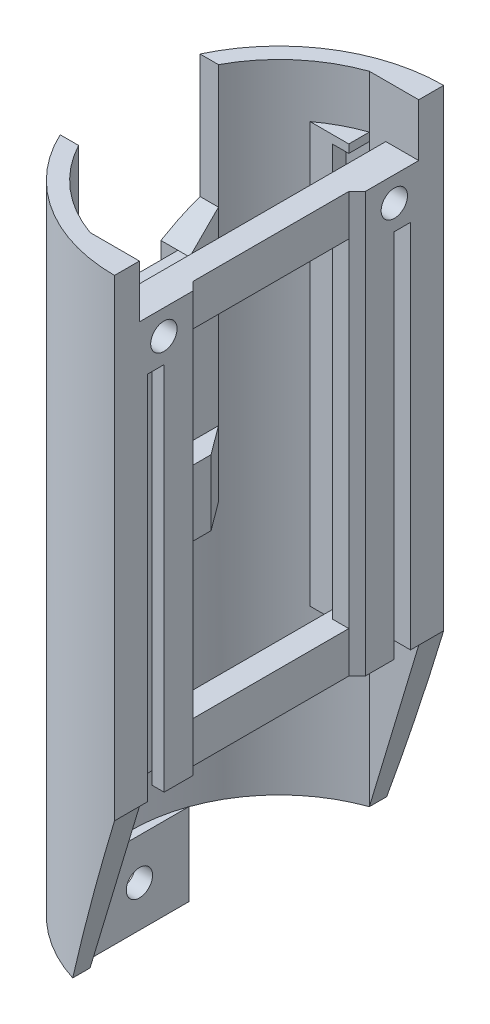
SolidWorks part; units mm, degrees
ref_plane "前视基准面" through (0, 0, 0) normal (0, 0, 1) x (1, 0, 0)
ref_plane "上视基准面" through (0, 0, 0) normal (0, 1, 0) x (1, 0, 0)
ref_plane "右视基准面" through (0, 0, 0) normal (1, 0, 0) x (0, 0, -1)
other "Configuration Table"
sketch "草图1" plane through (0, 0, 0) normal (0, 1, 0) x (1, 0, 0)
  line L0 (0, -473.638) -> (0, 23208.2609) construction
  line L1 (0, 0) -> (-4, 0) construction
  line L2 (0, 20) -> (0, -20)
  line L3 (-4, -17.5499) -> (-4, 17.5499)
  arc A0 (0, 20) -> (0, -20) centre (0, 0) ccw
  arc A1 (-4, 17.5499) -> (-4, -17.5499) centre (0, 0) ccw
  point P12 (-4, 0)
  dimension "D1" = 40
  dimension "D2" = 36
  dimension "D3" = 4
extrude "凸台-拉伸1" add sketch "草图1" along normal blind 70
sketch "草图3" plane through (0, 0, 0) normal (1, 0, 0) x (0, 0, -1)
  line L0 (-20, 0) -> (20, 0) construction
  line L1 (-16, 60) -> (16, 60) construction
  line L2 (-16, 60) -> (-16, 0) construction
  line L3 (-16, 0) -> (16, 0) construction
  line L4 (16, 60) -> (16, 0) construction
  line L5 (-20, 70) -> (20, 70) construction
  circle A0 centre (-14, 58) radius 2 construction
  circle A1 centre (14, 58) radius 2 construction
  circle A2 centre (-14, 58) radius 1
  circle A3 centre (14, 58) radius 1
  point P4 (0, 60)
  dimension "D4" = 4
  dimension "D5" = 4
  dimension "D6" = 2
  dimension "D7" = 2
  dimension "D1" = 0
  dimension "D2" = 10
  dimension "D3" = 32
extrude "切除-拉伸2" cut sketch "草图3" against normal up to surface (4 mm away) from surface up to face at (-4, 35, 0) starting at face at (0, 35, 0)
sketch "草图5" plane through (0, 0, 0) normal (0, 1, 0) x (1, 0, 0)
  line L0 (0, -1000) -> (0, 49000) construction
  line L1 (-1000, 0) -> (49000, 0) construction
  line L2 (-6, 16.9706) -> (6, 16.9706) construction
  line L3 (-6, -16.9706) -> (6, -16.9706) construction
  line L4 (0, 16.9706) -> (0, -16.9706)
  line L5 (0, -16.9706) -> (-4, -16.9706)
  line L6 (-4, -17.5499) -> (-4, 17.5499) construction
  line L7 (-4, -16.9706) -> (-4, 16.9706)
  line L8 (-4, 16.9706) -> (0, 16.9706)
  circle A0 centre (0, 0) radius 18 construction
  point P11 (0, 16.9706)
  dimension "D1" = 12
extrude "切除-拉伸4" cut sketch "草图5" against normal blind 9 from surface starting at face at (-10, 70, 0)
sketch "草图6" plane through (0, 0, 0) normal (0, 1, 0) x (1, 0, 0)
  line L0 (-4, 16.9706) -> (-6, 16.9706)
  line L1 (0, 16.9706) -> (0, 18)
  line L2 (-4, -16.9706) -> (-6, -16.9706)
  line L3 (0, -16.9706) -> (0, -18)
  line L4 (-4, 16.9706) -> (-4, -16.9706)
  line L5 (0, 16.9706) -> (-4, 16.9706)
  line L6 (0, -16.9706) -> (0, 16.9706)
  line L7 (-4, -16.9706) -> (0, -16.9706)
  line L9 (0, 16.9706) -> (-4, 16.9706)
  line L11 (-4, -16.9706) -> (0, -16.9706)
  arc A0 (0, 18) -> (-6, 16.9706) centre (0, 0) ccw
  arc A1 (-6, -16.9706) -> (0, -18) centre (0, 0) ccw
  dimension "D1" = 0
extrude "凸台-拉伸2" add sketch "草图6" against normal up to surface from surface up to face at (-10, 0, 0) starting at face at (-6.25, 70, 0)
sketch "草图7" plane through (0, 0, 0) normal (0, 1, 0) x (1, 0, 0)
  line L4 (-4, 16.9706) -> (-4, -16.9706)
  line L5 (0, 16.9706) -> (-4, 16.9706)
  line L6 (0, -16.9706) -> (0, 16.9706)
  line L7 (-4, -16.9706) -> (0, -16.9706)
  line L8 (-4, 16.9706) -> (-4, -16.9706)
  line L9 (0, 16.9706) -> (-4, 16.9706)
  line L10 (0, -16.9706) -> (0, 16.9706)
  line L11 (-4, -16.9706) -> (0, -16.9706)
  dimension "D1" = 0
extrude "切除-拉伸5" cut sketch "草图7" along normal blind 10
sketch "草图8" plane through (0, 0, 0) normal (0, 1, 0) x (1, 0, 0)
  line L0 (0, 16.9706) -> (0, -16.9706) construction
  line L1 (-6, 16.9706) -> (0, 16.9706)
  line L2 (-6, 16.9706) -> (-6, 14.4706)
  line L3 (-6, 14.4706) -> (0, 14.4706)
  line L4 (0, 16.9706) -> (0, 14.4706)
  line L6 (0, -16.9706) -> (-6, -16.9706)
  line L7 (0, -16.9706) -> (0, -14.4706)
  line L8 (0, -14.4706) -> (-6, -14.4706)
  line L9 (-6, -16.9706) -> (-6, -14.4706)
  dimension "D1" = 2.5
  dimension "D2" = 2.5
extrude "凸台-拉伸3" add sketch "草图8" against normal blind 1 from surface starting at face at (-2, 61, 0)
sketch "草图10" plane through (0, 0, 0) normal (0, 1, 0) x (1, 0, 0)
  line L0 (-6, 16.9706) -> (-6, 14.4706)
  line L1 (-6, 14.4706) -> (-10.7053, 14.4706)
  line L2 (-6, -14.4706) -> (-10.7053, -14.4706)
  line L3 (-6, -14.4706) -> (-6, -16.9706)
  arc A0 (-6, 16.9706) -> (-10.7053, 14.4706) centre (0, 0) ccw
  arc A1 (-10.7053, -14.4706) -> (-6, -16.9706) centre (0, 0) ccw
extrude "凸台-拉伸4" add sketch "草图10" along normal up to surface (70 mm away) from surface up to face at (-7.3333, 70, 0) starting at face at (-7.3333, 0, 0)
sketch "草图11" plane through (0, 0, 0) normal (0, 1, 0) x (1, 0, 0)
  line L0 (0, 16.9706) -> (0, -16.9706) construction
  line L1 (-6, 16.9706) -> (0, 16.9706)
  line L2 (-6, 16.9706) -> (-6, 14.4706)
  line L3 (-6, 14.4706) -> (0, 14.4706)
  line L4 (0, 16.9706) -> (0, 14.4706)
  line L5 (-6, 14.4706) -> (-10.7053, 14.4706) construction
  line L7 (-6, -14.4706) -> (0, -14.4706)
  line L8 (-6, -14.4706) -> (-6, -16.9706)
  line L9 (-6, -16.9706) -> (0, -16.9706)
  line L10 (0, -14.4706) -> (0, -16.9706)
  dimension "D1" = 0
extrude "凸台-拉伸5" add sketch "草图11" along normal up to surface (70 mm away) from surface up to face at (-7.2705, 70, 0) starting at face at (-4, 61, 0)
sketch "草图12" plane through (0, 0, 0) normal (0, 0, 1) x (1, 0, 0)
  line L1 (-6, 60) -> (-4, 60)
  line L2 (-6, 60) -> (-6, 61)
  line L3 (-6, 61) -> (-4, 61)
  line L4 (-4, 60) -> (-4, 61)
extrude "切除-拉伸6" cut sketch "草图12" against normal up to surface (16.9706 mm away) from surface up to face at (-3.3333, 23.3333, -16.9706) starting at face at (-3.3333, 23.3333, 16.9706)
sketch "草图14" plane through (0, 0, 0) normal (0, 1, 0) x (1, 0, 0)
  line L0 (-4, -14.4706) -> (-4, 14.4706) construction
  line L1 (-4, 10.4706) -> (-3, 10.4706)
  line L2 (-4, 10.4706) -> (-4, -10.4706)
  line L3 (-4, -10.4706) -> (-3, -10.4706)
  line L4 (-3, 10.4706) -> (-3, -10.4706)
  line L5 (-10.7053, -14.4706) -> (0, -14.4706) construction
  line L6 (-4, 14.4706) -> (0, 14.4706) construction
  line L7 (0, 14.4706) -> (0, -14.4706) construction
  line L8 (-1, 10.4706) -> (0, 10.4706)
  line L9 (-1, 10.4706) -> (-1, -10.4706)
  line L10 (-1, -10.4706) -> (0, -10.4706)
  line L11 (0, 10.4706) -> (0, -10.4706)
  line L12 (0, -14.4706) -> (-4, -14.4706) construction
  line L13 (0, 14.4706) -> (-10.7053, 14.4706) construction
  dimension "D1" = 1
  dimension "D2" = 4
  dimension "D3" = 4
  dimension "D4" = 1
  dimension "D5" = 4
  dimension "D6" = 4
extrude "切除-拉伸8" cut sketch "草图14" along normal up to surface (61 mm away) from surface up to face at (-2, 61, 0) starting at face at (-2, 10, 0)
sketch "草图15" plane through (0, 0, 0) normal (1, 0, 0) x (0, 0, -1)
  line L0 (10.4706, 61) -> (10.4706, 10) construction
  line L5 (-10.4706, 61) -> (-10.4706, 10) construction
  line L6 (10.4706, 61) -> (-10.4706, 61) construction
  line L7 (-10.4706, 10) -> (10.4706, 10) construction
  line L9 (-9.4706, 56) -> (9.4706, 56)
  line L10 (-9.4706, 56) -> (-9.4706, 15)
  line L11 (-9.4706, 15) -> (9.4706, 15)
  line L12 (9.4706, 56) -> (9.4706, 15)
  dimension "D1" = 1
  dimension "D2" = 1
  dimension "D3" = 5
  dimension "D4" = 5
extrude "切除-拉伸9" cut sketch "草图15" against normal up to surface (3 mm away) from surface up to face at (-3, 35.5, 0) starting at face at (-1, 35.5, 0)
sketch "草图17" plane through (0, 0, 0) normal (1, 0, 0) x (0, 0, -1)
  circle A0 centre (-14, 58) radius 1.6
  circle A1 centre (14, 58) radius 1.6
  dimension "D1" = 3.2
  dimension "D2" = 3.2
extrude "切除-拉伸10" cut sketch "草图17" against normal blind 2.5
sketch "草图20" plane through (0, 0, 0) normal (0, 1, 0) x (1, 0, 0)
  line L0 (-1, 10.4706) -> (0, 10.4706)
  line L1 (0, 14.4706) -> (0, 10.4706) construction
  line L2 (0, 10.4706) -> (-1, 10.4706) construction
  line L3 (0, 10.4706) -> (-1, 9.4706)
  line L4 (-1, 10.4706) -> (-1, -10.4706) construction
  line L5 (-1, 9.4706) -> (-1, 10.4706)
  line L6 (-4, 10.4706) -> (-3, 10.4706)
  line L7 (-3, 10.4706) -> (-3, 9.4706)
  line L8 (-3, -10.4706) -> (-3, 10.4706) construction
  line L9 (-3, 9.4706) -> (-4, 10.4706)
  line L10 (-4, -10.4706) -> (-3, -10.4706)
  line L11 (-3, -10.4706) -> (-3, -9.4706)
  line L12 (-3, -9.4706) -> (-4, -10.4706)
  line L13 (0, -10.4706) -> (-1, -10.4706)
  line L14 (-1, -10.4706) -> (0, -10.4706) construction
  line L15 (-1, -10.4706) -> (-1, -9.4706)
  line L16 (-1, -9.4706) -> (0, -10.4706)
  dimension "D1" = 1
  dimension "D2" = 1
  dimension "D3" = 1
  dimension "D4" = 1
  dimension "D5" = 1
extrude "凸台-拉伸11" add sketch "草图20" against normal up to surface (-10 mm away) from surface up to face at (-2, 10, 0) starting at face at (-2, 61, 0)
sketch "草图21" plane through (0, 0, 0) normal (0, 1, 0) x (1, 0, 0)
  line L0 (-4, 10.4706) -> (-4, -10.4706)
  line L1 (-4, -10.4706) -> (-3, -9.4706)
  line L2 (-3, -9.4706) -> (-3, 9.4706)
  line L3 (-3, 9.4706) -> (-4, 10.4706)
extrude "凸台-拉伸12" add sketch "草图21" against normal up to surface (-56 mm away) from surface up to face at (-2, 56, 0) starting at face at (-2, 61, 0)
sketch "草图22" plane through (0, 0, 0) normal (0, 1, 0) x (1, 0, 0)
  line L4 (-4, 10.4706) -> (-4, -10.4706)
  line L5 (-4, -10.4706) -> (-3, -9.4706)
  line L6 (-3, -9.4706) -> (-3, 9.4706)
  line L7 (-3, 9.4706) -> (-4, 10.4706)
  line L8 (-4, 10.4706) -> (-4, -10.4706)
  line L9 (-4, -10.4706) -> (-3, -9.4706)
  line L10 (-3, -9.4706) -> (-3, 9.4706)
  line L11 (-3, 9.4706) -> (-4, 10.4706)
  dimension "D1" = 0
extrude "凸台-拉伸13" add sketch "草图22" along normal up to surface (15 mm away) from surface up to face at (-2, 15, 0) starting at face at (-2, 10, 0)
sketch "草图23" plane through (0, 0, 0) normal (0, 0, 1) x (1, 0, 0)
  line L0 (-3, 56) -> (-1, 56) construction
  line L1 (-6, 61) -> (-8, 61)
  line L2 (-6, 61) -> (-6, 55)
  line L3 (-6, 55) -> (-8, 55)
  line L4 (-8, 61) -> (-8, 55)
  dimension "D1" = 1
  dimension "D2" = 2
extrude "切除-拉伸11" cut sketch "草图23" along normal up to surface (1.654 mm away) from surface up to face at (-14.3526, 35, 0) starting at face at (-5.3444, 46.1429, 14.4706)
sketch "草图24" plane through (0, 0, 0) normal (0, 0, 1) x (1, 0, 0)
  line L4 (-6, 61) -> (-8, 61)
  line L5 (-8, 61) -> (-8, 55)
  line L6 (-8, 55) -> (-6, 55)
  line L7 (-6, 55) -> (-6, 61)
  line L8 (-6, 61) -> (-8, 61)
  line L9 (-8, 61) -> (-8, 55)
  line L10 (-8, 55) -> (-6, 55)
  line L11 (-6, 55) -> (-6, 61)
  dimension "D1" = 0
extrude "切除-拉伸12" cut sketch "草图24" against normal up to surface (16.1245 mm away) up to face at (-14.3526, 35, 0)
sketch "草图25" plane through (0, 0, 0) normal (0, 1, 0) x (1, 0, 0)
  line L0 (-6, -16.9706) -> (-6, -14.4706)
  line L1 (-8, -14.4706) -> (-4, -14.4706) construction
  line L2 (-6, -14.4706) -> (-10.7053, -14.4706)
  line L3 (-10.7053, 14.4706) -> (-6, 14.4706)
  line L4 (-4, 14.4706) -> (-8, 14.4706) construction
  line L5 (-6, 14.4706) -> (-6, 16.9706)
  arc A0 (-10.7053, -14.4706) -> (-6, -16.9706) centre (0, 0) ccw
  arc A1 (-6, 16.9706) -> (-10.7053, 14.4706) centre (0, 0) ccw
extrude "切除-拉伸13" cut sketch "草图25" along normal up to surface (10 mm away) from surface up to face at (-1.25, 10, 0) starting at face at (-7.2705, 0, 0)
sketch "草图29" plane through (0, 0, 0) normal (0, 1, 0) x (1, 0, 0)
  line L0 (0, -16.9706) -> (0, -14.4706)
  line L1 (0, -14.4706) -> (-10.7053, -14.4706)
  line L2 (0, -16.9706) -> (-6, -16.9706)
  line L3 (-4, -16.9706) -> (-6, -16.9706)
  line L4 (0, -18) -> (0, -16.9706)
  line L5 (0, -16.9706) -> (-4, -16.9706)
  line L6 (-4, -16.9706) -> (-6, -16.9706) construction
  line L8 (0, -16.9706) -> (-4, -16.9706) construction
  line L9 (-6, 16.9706) -> (-4, 16.9706)
  line L10 (0, 16.9706) -> (0, 18)
  line L11 (-4, 16.9706) -> (0, 16.9706)
  line L12 (-6, 16.9706) -> (-4, 16.9706) construction
  line L14 (-4, 16.9706) -> (0, 16.9706) construction
  line L15 (-6, 16.9706) -> (0, 16.9706)
  line L16 (0, 16.9706) -> (0, 14.4706)
  line L17 (0, 14.4706) -> (-10.7053, 14.4706)
  arc A0 (-10.7053, -14.4706) -> (-6, -16.9706) centre (0, 0) ccw
  arc A1 (-6, -16.9706) -> (0, -18) centre (0, 0) ccw
  arc A3 (0, 18) -> (-6, 16.9706) centre (0, 0) ccw
  arc A5 (-6, 16.9706) -> (-10.7053, 14.4706) centre (0, 0) ccw
  dimension "D1" = 0
  dimension "D2" = 0
extrude "切除-拉伸18" cut sketch "草图29" against normal up to surface (-61 mm away) from surface up to face at (-1.25, 61, 0) starting at face at (-8.1175, 70, 0)
sketch "草图30" plane through (0, 0, 0) normal (0, 1, 0) x (1, 0, 0)
  line L0 (-8, 16.1245) -> (-8, 14.4706)
  line L1 (-8, 14.4706) -> (-4, 14.4706)
  line L2 (-4, -16.9706) -> (-4, 16.9706) construction
  line L3 (-4, 14.4706) -> (-4, 16.9706)
  line L4 (-6, 16.9706) -> (0, 16.9706) construction
  line L5 (-4, 16.9706) -> (-6, 16.9706)
  line L6 (-8, -16.1245) -> (-8, -14.4706)
  line L7 (-8, -14.4706) -> (-4, -14.4706)
  line L8 (-4, -14.4706) -> (-4, -16.9706)
  line L9 (-4, -16.9706) -> (-6, -16.9706)
  arc A0 (-6, 16.9706) -> (-8, 16.1245) centre (0, 0) ccw
  arc A1 (-8, -16.1245) -> (-6, -16.9706) centre (0, 0) ccw
extrude "凸台-拉伸16" add sketch "草图30" against normal blind 1 from surface starting at face at (-8.9139, 61, -15.0418)
sketch "草图31" plane through (0, 0, 0) normal (0, 1, 0) x (1, 0, 0)
  line L4 (0, -20) -> (0, -16.9706)
  line L5 (0, -16.9706) -> (-6, -16.9706)
  line L6 (-6, 16.9706) -> (0, 16.9706)
  line L7 (0, 16.9706) -> (0, 20)
  line L8 (0, -20) -> (0, -16.9706)
  line L9 (0, -16.9706) -> (-6, -16.9706)
  line L10 (-6, 16.9706) -> (0, 16.9706)
  line L11 (0, 16.9706) -> (0, 20)
  arc A2 (-6, 16.9706) -> (-6, -16.9706) centre (0, 0) ccw
  arc A3 (0, 20) -> (0, -20) centre (0, 0) ccw
  arc A4 (-6, 16.9706) -> (-6, -16.9706) centre (0, 0) ccw
  arc A5 (0, 20) -> (0, -20) centre (0, 0) ccw
  dimension "D1" = 0
extrude "凸台-拉伸17" add sketch "草图31" along normal blind 2.4 from surface starting at face at (-7.3333, 70, 0)
sketch "草图32" plane through (0, 0, 0) normal (0, 1, 0) x (1, 0, 0)
  line L4 (0, 16.9706) -> (0, 20)
  line L5 (0, -20) -> (0, -16.9706)
  line L6 (0, -16.9706) -> (-6, -16.9706)
  line L7 (-6, 16.9706) -> (0, 16.9706)
  line L8 (0, 16.9706) -> (0, 20)
  line L9 (0, -20) -> (0, -16.9706)
  line L10 (0, -16.9706) -> (-6, -16.9706)
  line L11 (-6, 16.9706) -> (0, 16.9706)
  arc A2 (0, 20) -> (0, -20) centre (0, 0) ccw
  arc A3 (-6, 16.9706) -> (-6, -16.9706) centre (0, 0) ccw
  arc A4 (0, 20) -> (0, -20) centre (0, 0) ccw
  arc A5 (-6, 16.9706) -> (-6, -16.9706) centre (0, 0) ccw
  dimension "D1" = 0
extrude "切除-拉伸19" cut sketch "草图32" against normal blind 5 from surface starting at face at (-7.3333, 72.4, 0)
sketch "草图33" plane through (0, 0, 0) normal (0, 1, 0) x (1, 0, 0)
  line L0 (-1000, 0) -> (49000, 0) construction
  line L1 (-17.2916, -5) -> (-17.2916, 5)
  line L2 (-17.2916, 5) -> (-19.3649, 5)
  line L3 (-17.2916, -5) -> (-19.3649, -5)
  arc A0 (-17.2916, 5) -> (-17.2916, -5) centre (0, 0) ccw construction
  arc A1 (-19.3649, 5) -> (-19.3649, -5) centre (0, 0) ccw
  point P11 (-17.2916, 0)
  dimension "D1" = 10
extrude "切除-拉伸20" cut sketch "草图33" against normal blind 45 from surface starting at face at (-7.3333, 67.4, 0)
sketch "草图39" plane through (0, 0, 0) normal (0, 1, 0) x (1, 0, 0)
  line L0 (-20, 0) -> (-15.8666, 0) construction
  line L1 (-15.8666, -8.5) -> (-15.8666, 8.5)
  line L2 (-15.8666, 8.5) -> (-18.1039, 8.5)
  line L3 (-15.8666, -8.5) -> (-18.1039, -8.5)
  arc A0 (-18.1039, 8.5) -> (-18.1039, -8.5) centre (0, 0) ccw
  arc A1 (-15.8666, 8.5) -> (-15.8666, -8.5) centre (0, 0) ccw construction
  point P11 (-15.8666, 0)
  dimension "D1" = 17
extrude "切除-拉伸22" cut sketch "草图39" against normal blind 15 from surface contours L2 A0 L3 L1 region at (-17.6683, 0, 0) starting at face at (-9.3339, 67.4, -13.7237)
sketch "草图40" plane through (0, 0, 0) normal (1, 0, 0) x (0, 0, -1)
  line L0 (-5, 52.4) -> (-8.5, 52.4)
  line L1 (-8.5, 52.4) -> (-5, 48.9)
  line L2 (-5, 22.4) -> (-5, 52.4) construction
  line L3 (-5, 48.9) -> (-5, 52.4)
  line L4 (8.5, 52.4) -> (5, 52.4)
  line L5 (5, 52.4) -> (5, 48.9)
  line L6 (5, 22.4) -> (5, 52.4) construction
  line L7 (5, 48.9) -> (8.5, 52.4)
  dimension "D1" = 3.5
  dimension "D2" = 3.5
extrude "切除-拉伸25" cut sketch "草图40" against normal through all
sketch "草图41" plane through (0, 0, 0) normal (0, 1, 0) x (1, 0, 0)
  line L0 (-1000, 0) -> (49000, 0) construction
  line L1 (-15.8666, 8.5) -> (-15.8666, -8.5)
  line L2 (-17.2916, 5) -> (-17.2916, -5)
  arc A0 (-17.2916, -5) -> (-15.8666, -8.5) centre (0, 0) ccw
  arc A1 (-15.8666, 8.5) -> (-17.2916, 5) centre (0, 0) ccw
extrude "凸台-拉伸24" add sketch "草图41" along normal up to vertex (48.9 mm away) from surface up to point (-19.3649, 48.9, -5) starting at face at (-18.6641, 22.4, 0)
sketch "草图42" plane through (0, 0, 0) normal (1, 0, 0) x (0, 0, -1)
  line L0 (-8.5, 52.4) -> (-8.5, 48.9)
  line L1 (-8.5, 48.9) -> (-5, 48.9)
  line L2 (-5, 48.9) -> (-8.5, 52.4)
  line L3 (8.5, 52.4) -> (8.5, 48.9)
  line L4 (8.5, 48.9) -> (5, 48.9)
  line L5 (5, 48.9) -> (8.5, 52.4)
extrude "凸台-拉伸25" add sketch "草图42" against normal up to surface (2.2372 mm away) from surface up to face at (-14.5014, 43.0882, 0) starting at face at (-15.8666, 35.65, 0)
sketch "草图43" plane through (0, 0, 0) normal (0, 1, 0) x (1, 0, 0)
  line L0 (-15.8666, 8.5) -> (-15.8666, -8.5)
  arc A0 (-15.8666, 8.5) -> (-15.8666, -8.5) centre (0, 0) ccw
extrude "凸台-拉伸26" add sketch "草图43" against normal blind 1 from surface starting at face at (-16.6252, 22.4, 0)
sketch "草图44" plane through (0, 0, 0) normal (0, 1, 0) x (1, 0, 0)
  line L0 (-1000, 0) -> (49000, 0) construction
  line L1 (-15.8666, 0) -> (-13.2666, 0) construction
  line L2 (-15.8666, 5) -> (-15.8666, -5) construction
  line L3 (-13.2666, -5) -> (-13.2666, 5)
  line L4 (-13.2666, 5) -> (-15.8666, 8.5)
  line L5 (-13.2666, -5) -> (-15.8666, -8.5)
  line L6 (-15.8666, 8.5) -> (-15.8666, -8.5)
  circle A1 centre (0, 0) radius 18 construction
  point P12 (-13.2666, 0)
  dimension "D1" = 2.6
  dimension "D2" = 10
extrude "凸台-拉伸27" add sketch "草图44" along normal blind 8 from surface starting at face at (-16.9333, 21.4, 0)
sketch "草图45" plane through (0, 0, 0) normal (1, 0, 0) x (0, 0, -1)
  line L0 (0, 67.4) -> (0, 21.4) construction
  line L2 (5, 22.4) -> (-5, 22.4) construction
  circle A0 centre (0, 26.4) radius 1
  dimension "D1" = 2
  dimension "D2" = 4
extrude "切除-拉伸26" cut sketch "草图45" along normal up to surface (-13.2666 mm away) from surface up to face at (-13.2666, 25.4, 0) starting at face at (-17.2916, 35.65, 0)
sketch "草图46" plane through (0, 0, 0) normal (0, 1, 0) x (1, 0, 0)
  line L0 (-15.8666, 5) -> (-15.8666, -5) construction
  line L1 (-15.8666, 2) -> (-14.2666, 2)
  line L2 (-15.8666, 2) -> (-15.8666, -2)
  line L3 (-15.8666, -2) -> (-14.2666, -2)
  line L4 (-14.2666, 2) -> (-14.2666, -2)
  line L5 (-17.2916, -5) -> (-17.2916, 5) construction
  point P8 (-17.2916, 0)
  point P9 (-15.8666, 0)
  dimension "D1" = 4
  dimension "D2" = 1.6
extrude "切除-拉伸27" cut sketch "草图46" along normal blind 5 from surface starting at face at (-15.1, 21.4, 0)
sketch "草图47" plane through (0, 0, 0) normal (1, 0, 0) x (0, 0, -1)
  line L1 (0, 24.0906) -> (2, 25.2453)
  line L2 (2, 25.2453) -> (2, 27.5547)
  line L3 (2, 27.5547) -> (0, 28.7094)
  line L4 (0, 28.7094) -> (-2, 27.5547)
  line L5 (-2, 27.5547) -> (-2, 25.2453)
  line L6 (-2, 25.2453) -> (0, 24.0906)
  circle A0 centre (0, 26.4) radius 2 construction
  dimension "D1" = 4
extrude "切除-拉伸28" cut sketch "草图47" against normal up to surface (15.8666 mm away) from surface up to face at (-15.8666, 24.5667, 0) starting at face at (-14.2666, 24.5667, 0)
sketch "草图48" plane through (0, 0, 0) normal (1, 0, 0) x (0, 0, -1)
  line L0 (5, 22.4) -> (3, 22.4)
  line L1 (5, 22.4) -> (-5, 22.4) construction
  line L2 (3, 22.4) -> (5, 24.4)
  line L3 (5, 22.4) -> (5, 48.9) construction
  line L4 (5, 24.4) -> (5, 22.4)
  line L5 (-5, 22.4) -> (-5, 24.4)
  line L6 (-5, 22.4) -> (-5, 48.9) construction
  line L7 (-5, 24.4) -> (-3, 22.4)
  line L8 (-3, 22.4) -> (-5, 22.4)
  dimension "D1" = 2
  dimension "D2" = 2
  dimension "D3" = 2
  dimension "D4" = 2
extrude "凸台-拉伸28" add sketch "草图48" against normal up to surface (2.0733 mm away) from surface up to face at (-14.5014, 43.0882, 0) starting at face at (-17.2916, 26.4, 1)
sketch "草图49" plane through (0, 0, 0) normal (0, 1, 0) x (1, 0, 0)
  line L1 (-6, -16.9706) -> (-4, -16.9706)
  line L2 (-6, -16.9706) -> (-6, 16.9706)
  line L3 (-6, 16.9706) -> (-4, 16.9706)
  line L4 (-4, -16.9706) -> (-4, 16.9706)
extrude "切除-拉伸29" cut sketch "草图49" along normal through all
sketch "草图50" plane through (0, 0, 0) normal (0, 1, 0) x (1, 0, 0)
  line L0 (0, 16.9706) -> (0, 15.9706) construction
  line L1 (0, 16.9706) -> (0, 10.4706) construction
  line L2 (0, 15.9706) -> (-3, 15.9706)
  line L3 (-3, 15.9706) -> (-3, 11.9706)
  line L4 (-3, 11.9706) -> (-1.5, 11.9706)
  line L5 (-1.5, 11.9706) -> (-1.5, 13.9706)
  line L6 (-1.5, 13.9706) -> (0, 13.9706)
  line L7 (-1000, 0) -> (49000, 0) construction
  line L8 (-1.5, -13.9706) -> (0, -13.9706)
  line L9 (-1.5, -11.9706) -> (-1.5, -13.9706)
  line L10 (-3, -11.9706) -> (-1.5, -11.9706)
  line L11 (-3, -15.9706) -> (-3, -11.9706)
  line L12 (0, -15.9706) -> (-3, -15.9706)
  line L13 (0, -16.9706) -> (0, -15.9706) construction
  line L14 (0, 15.9706) -> (0, 13.9706)
  line L15 (0, -13.9706) -> (0, -15.9706)
  dimension "D1" = 1
  dimension "D2" = 3
  dimension "D3" = 1.5
  dimension "D4" = 2
  dimension "D5" = 2
extrude "切除-拉伸30" cut sketch "草图50" along normal blind 45 from surface starting at face at (-1.25, 10, 0)
sketch "草图51" plane through (0, 0, 0) normal (0, 1, 0) x (1, 0, 0)
  line L0 (0, -11.9706) -> (3, -11.9706)
  line L1 (0, -13.9706) -> (0, -10.4706) construction
  line L2 (3, -11.9706) -> (3, -14.9706)
  line L3 (3, -14.9706) -> (0, -14.9706) construction
  line L4 (1.5, -14.9706) -> (1.5, -13.9706)
  line L5 (1.5, -13.9706) -> (0, -13.9706)
  line L6 (-3, -11.9706) -> (-1.5, -11.9706) construction
  line L7 (1.5, -14.9706) -> (3, -14.9706)
  line L8 (0, -13.9706) -> (0, -11.9706)
  line L9 (-1000, 0) -> (49000, 0) construction
  line L10 (3, 14.9706) -> (0, 14.9706) construction
  line L11 (0, 13.9706) -> (0, 11.9706)
  line L12 (1.5, 14.9706) -> (3, 14.9706)
  line L13 (1.5, 13.9706) -> (0, 13.9706)
  line L14 (1.5, 14.9706) -> (1.5, 13.9706)
  line L15 (3, 11.9706) -> (3, 14.9706)
  line L16 (0, 11.9706) -> (3, 11.9706)
  dimension "D1" = 3
  dimension "D2" = 3
  dimension "D3" = 3
extrude "凸台-拉伸29" add sketch "草图51" along normal blind 45 from surface starting at face at (-1.4, 10, 0)
sketch "草图52" plane through (0, 0, 0) normal (0, 1, 0) x (1, 0, 0)
  line L4 (0, -16.9706) -> (-6, -16.9706)
  line L5 (0, -20) -> (0, -16.9706)
  line L6 (0, 16.9706) -> (0, 20)
  line L7 (-6, 16.9706) -> (0, 16.9706)
  line L8 (0, -16.9706) -> (-6, -16.9706)
  line L9 (0, -20) -> (0, -16.9706)
  line L10 (0, 16.9706) -> (0, 20)
  line L11 (-6, 16.9706) -> (0, 16.9706)
  arc A2 (-6, 16.9706) -> (-6, -16.9706) centre (0, 0) ccw
  arc A3 (0, 20) -> (0, -20) centre (0, 0) ccw
  arc A4 (-6, 16.9706) -> (-6, -16.9706) centre (0, 0) ccw
  arc A5 (0, 20) -> (0, -20) centre (0, 0) ccw
  dimension "D1" = 0
extrude "凸台-拉伸30" add sketch "草图52" against normal blind 10
sketch "草图58" plane through (0, 0, 0) normal (0, 1, 0) x (1, 0, 0)
  line L0 (1.5, -13.9706) -> (1.5, -14.9706) construction
  line L1 (1.5, -14.9706) -> (3, -14.9706) construction
  line L2 (3, -14.9706) -> (3, -11.9706) construction
  line L3 (3, -11.9706) -> (0, -11.9706) construction
  line L4 (0, -11.9706) -> (0, -13.9706) construction
  line L5 (0, -13.9706) -> (1.5, -13.9706) construction
  line L6 (1.5, 13.9706) -> (0, 13.9706) construction
  line L7 (0, 13.9706) -> (0, 11.9706) construction
  line L8 (0, 11.9706) -> (3, 11.9706) construction
  line L9 (3, 11.9706) -> (3, 14.9706) construction
  line L10 (3, 14.9706) -> (1.5, 14.9706) construction
  line L11 (1.5, 14.9706) -> (1.5, 13.9706) construction
  line L12 (1.5, -13.9706) -> (1.5, -14.9706)
  line L13 (1.5, -14.9706) -> (3, -14.9706)
  line L14 (3, -14.9706) -> (3, -11.9706)
  line L15 (3, -11.9706) -> (0, -11.9706)
  line L16 (0, -11.9706) -> (0, -13.9706)
  line L17 (0, -13.9706) -> (1.5, -13.9706)
  line L18 (1.5, 13.9706) -> (0, 13.9706)
  line L19 (0, 13.9706) -> (0, 11.9706)
  line L20 (0, 11.9706) -> (3, 11.9706)
  line L21 (3, 11.9706) -> (3, 14.9706)
  line L22 (3, 14.9706) -> (1.5, 14.9706)
  line L23 (1.5, 14.9706) -> (1.5, 13.9706)
extrude "切除-拉伸34" cut sketch "草图58" along normal up to surface (55 mm away) from surface up to face at (1.5, 55, 13.6372) starting at face at (-0.3571, 10, 0)
sketch "草图60" plane through (0, 0, 0) normal (0, 0, 1) x (1, 0, 0)
  line L0 (0, 10) -> (-6, -10)
  line L1 (-6, -10) -> (0, -10)
  line L2 (0, -10) -> (0, 10)
extrude "切除-拉伸35" cut sketch "草图60" against normal through all and the other way through all
sketch "草图61" plane through (0, 0, 0) normal (0, 1, 0) x (1, 0, 0)
  line L0 (-1000, 0) -> (49000, 0) construction
  line L1 (-16.9706, 6) -> (-16.9706, -6)
  line L2 (-16.9706, -6) -> (-19.0788, -6)
  line L3 (-16.9706, 6) -> (-19.0788, 6)
  arc A0 (-19.0788, 6) -> (-19.0788, -6) centre (0, 0) ccw
  arc A1 (-16.9706, 6) -> (-16.9706, -6) centre (0, 0) ccw construction
  point P11 (-16.9706, 0)
  dimension "D1" = 12
extrude "凸台-拉伸32" add sketch "草图61" against normal blind 10 from surface starting at face at (-12.5, -10, 0)
sketch "草图62" plane through (0, 0, 0) normal (0, 1, 0) x (1, 0, 0)
  line L0 (-19.0788, -6) -> (-19.0788, 6)
  arc A0 (-19.0788, 6) -> (-19.0788, -6) centre (0, 0) ccw construction
  arc A1 (-19.0788, 6) -> (-19.0788, -6) centre (0, 0) ccw
extrude "切除-拉伸36" cut sketch "草图62" against normal blind 10 from surface starting at face at (-12.7237, -10, 12.7237)
sketch "草图63" plane through (0, 0, 0) normal (1, 0, 0) x (0, 0, -1)
  line L0 (-6, -20) -> (6, -20) construction
  line L1 (6, -20) -> (6, -10) construction
  circle A0 centre (0, -15) radius 1.6
  dimension "D1" = 3.2
  dimension "D2" = 5
  dimension "D3" = 6
extrude "切除-拉伸37" cut sketch "草图63" against normal through all
sketch "草图65" plane through (0, 0, 0) normal (1, 0, 0) x (0, 0, -1)
  line L0 (-6, -10) -> (6, -10)
  line L3 (6, -10) -> (6, -14)
  line L11 (6, -20) -> (6, -10) construction
  line L12 (6, -14) -> (3, -11)
  line L13 (3, -11) -> (-3, -11)
  line L14 (-3, -11) -> (-6, -14)
  line L15 (-6, -20) -> (-6, -10) construction
  line L16 (-6, -14) -> (-6, -10)
  dimension "D1" = 4
  dimension "D2" = 6
  dimension "D3" = 3
  dimension "D4" = 4
  dimension "D5" = 3
extrude "凸台-拉伸33" add sketch "草图65" against normal up to surface from surface up to face at (-13.7534, 30.313, 0) starting at face at (-19.0788, -15, -1.6)
